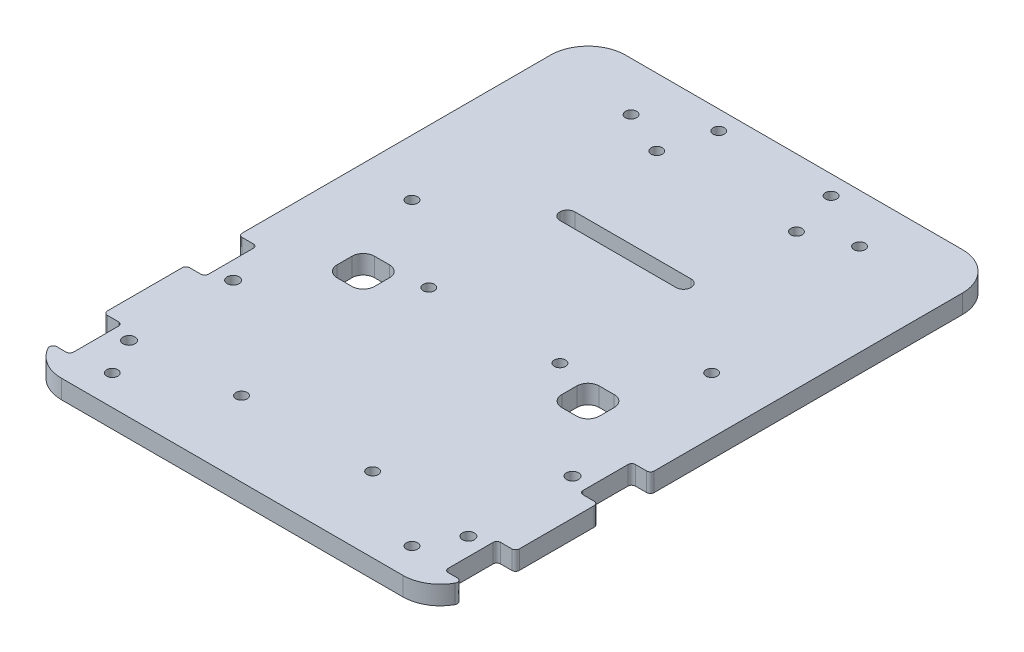
SolidWorks part; units mm, degrees
ref_plane "Front Plane" through (0, 0, 0) normal (0, 0, 1) x (1, 0, 0)
ref_plane "Top Plane" through (0, 0, 0) normal (0, 1, 0) x (1, 0, 0)
ref_plane "Right Plane" through (0, 0, 0) normal (1, 0, 0) x (0, 0, -1)
sketch "Sketch1" plane through (0, 0, 0) normal (0, 1, 0) x (1, 0, 0)
  line L0 (0, -75) -> (0, -43.3378) construction
  line L1 (-55, 75) -> (55, 75)
  line L2 (-55, 75) -> (-55, -75)
  line L3 (-55, -75) -> (55, -75)
  line L4 (55, 75) -> (55, -75)
  line L5 (-55, 75) -> (55, -75) construction
  line L6 (-55, -75) -> (55, 75) construction
  line L7 (-55, -43.3378) -> (55, -43.3378)
  line L8 (-55, -43.3378) -> (-45.3, -43.3378) construction
  line L9 (55, -43.3378) -> (45.3, -43.3378) construction
  line L10 (-45.3, -29.4378) -> (-45.3, -57.2378)
  line L11 (45.3, -29.4378) -> (45.3, -57.2378)
  line L12 (0, 75) -> (0, 62) construction
  line L13 (-30.5, 62) -> (30.5, 62)
  line L14 (0, 75) -> (0, 57) construction
  line L15 (-18.65, 57) -> (18.65, 57)
  line L16 (0, 75) -> (0, 30) construction
  line L17 (-55, 13) -> (55, 13) construction
  line L18 (-17.5, 32) -> (17.5, 32)
  line L19 (-17.5, 32) -> (-17.5, 28)
  line L20 (-17.5, 28) -> (17.5, 28)
  line L21 (17.5, 32) -> (17.5, 28)
  line L22 (-17.5, 32) -> (17.5, 28) construction
  line L23 (-17.5, 28) -> (17.5, 32) construction
  line L24 (-40, 13) -> (-40, -67) construction
  line L25 (40, 13) -> (40, -67) construction
  line L26 (-15, 69.8972) -> (15, 69.8972)
  line L27 (-35, -5) -> (-25, -5)
  line L28 (-35, -5) -> (-35, -15)
  line L29 (-35, -15) -> (-25, -15)
  line L30 (-25, -5) -> (-25, -15)
  line L31 (-35, -5) -> (-25, -15) construction
  line L32 (-35, -15) -> (-25, -5) construction
  line L33 (25, -5) -> (35, -5)
  line L34 (25, -5) -> (25, -15)
  line L35 (25, -15) -> (35, -15)
  line L36 (35, -5) -> (35, -15)
  line L37 (25, -5) -> (35, -15) construction
  line L38 (25, -15) -> (35, -5) construction
  line L39 (0, -75) -> (0, 28) construction
  line L40 (-17.5, -5) -> (17.5, -5)
  line L41 (-17.5, -55) -> (17.5, -55)
  line L42 (55, -43.3378) -> (55, -58.3378) construction
  line L43 (55, -43.3378) -> (55, -28.3378) construction
  line L50 (50, -18.3378) -> (55, -18.3378)
  line L51 (50, -18.3378) -> (50, -32.3378)
  line L52 (50, -32.3378) -> (55, -32.3378)
  line L53 (55, -18.3378) -> (55, -32.3378)
  line L54 (50, -54.3378) -> (55, -54.3378)
  line L55 (55, -68.3378) -> (55, -54.3378)
  line L56 (50, -68.3378) -> (55, -68.3378)
  line L57 (50, -68.3378) -> (50, -54.3378)
  line L58 (-50, -68.3378) -> (-50, -54.3378)
  line L59 (-50, -68.3378) -> (-55, -68.3378)
  line L60 (-55, -68.3378) -> (-55, -54.3378)
  line L61 (-50, -54.3378) -> (-55, -54.3378)
  line L62 (-50, -32.3378) -> (-55, -32.3378)
  line L63 (-55, -18.3378) -> (-55, -32.3378)
  line L64 (-50, -18.3378) -> (-55, -18.3378)
  line L65 (-50, -18.3378) -> (-50, -32.3378)
  circle A0 centre (-45.3, -29.4378) radius 1.6
  circle A1 centre (-45.3, -57.2378) radius 1.6
  circle A2 centre (45.3, -57.2378) radius 1.6
  circle A3 centre (45.3, -29.4378) radius 1.6
  circle A4 centre (30.5, 62) radius 1.5
  circle A5 centre (-30.5, 62) radius 1.5
  circle A6 centre (18.65, 57) radius 1.5
  circle A7 centre (-18.65, 57) radius 1.5
  circle A8 centre (-40, 13) radius 1.5
  circle A9 centre (40, 13) radius 1.5
  circle A10 centre (-40, -67) radius 1.5
  circle A11 centre (40, -67) radius 1.5
  circle A12 centre (-15, 69.8972) radius 1.5
  circle A13 centre (15, 69.8972) radius 1.5
  circle A14 centre (-17.5, -5) radius 1.5
  circle A15 centre (17.5, -5) radius 1.5
  circle A16 centre (-17.5, -55) radius 1.5
  circle A17 centre (17.5, -55) radius 1.5
  point P0 (0, 0)
  point P11 (0, -43.3378)
  point P16 (-45.3, -43.3378)
  point P19 (45.3, -43.3378)
  point P28 (0, 62)
  point P34 (0, 57)
  point P51 (-30, -10)
  point P56 (-30, -15)
  point P57 (30, -10)
  point P65 (0, 69.8972)
  point P71 (0, -5)
  point P74 (0, -55)
  dimension "D7" = 3.2
  dimension "D8" = 3.2
  dimension "D9" = 3.2
  dimension "D10" = 3.2
  dimension "D13" = 3
  dimension "D14" = 3
  dimension "D17" = 3
  dimension "D18" = 3
  dimension "D23" = 3
  dimension "D24" = 3
  dimension "D25" = 15
  dimension "D26" = 15
  dimension "D27" = 80
  dimension "D30" = 3
  dimension "D31" = 3
  dimension "D41" = 3
  dimension "D42" = 3
  dimension "D47" = 3
  dimension "D48" = 3
  dimension "D49" = 3
  dimension "D50" = 3
  dimension "D1" = 110
  dimension "D2" = 150
  dimension "D3" = 9.7
  dimension "D4" = 9.7
  dimension "D5" = 27.8
  dimension "D6" = 27.8
  dimension "D11" = 13
  dimension "D12" = 61
  dimension "D15" = 18
  dimension "D16" = 37.3
  dimension "D19" = 45
  dimension "D20" = 4
  dimension "D21" = 35
  dimension "D22" = 62
  dimension "D28" = 80
  dimension "D29" = 80
  dimension "D32" = 20
  dimension "D33" = 60
  dimension "D34" = 10
  dimension "D35" = 10
  dimension "D36" = 20
  dimension "D37" = 60
  dimension "D38" = 10
  dimension "D39" = 10
  dimension "D40" = 30
  dimension "D43" = 35
  dimension "D44" = 35
  dimension "D45" = 20
  dimension "D46" = 70
  dimension "D51" = 15
  dimension "D52" = 15
  dimension "D53" = 0
  dimension "D54" = 4
  dimension "D55" = 14
  dimension "D56" = 5
extrude "Boss-Extrude1" add sketch "Sketch1" along normal blind 5 contours A2 L7 A1 L2 L3 L4 A11 A10 | A3 L7 L4 L1 L2 A0 A9 A8 A7 A6 A5 A4 L18 L21 L20 L19 L27 L30 L29 L28 L33 L36 L35 L34 region at (0, 0, -16.4744) region at (0, 0, 59.0706)
fillet "Fillet1" radius 10 4 edges at (55, 2.5, -75) (55, 2.5, 75) (-55, 2.5, 75) (-55, 2.5, -75)
fillet "Fillet2" radius 2 4 edges at (-17.5, 2.5, -28) (-17.5, 2.5, -32) (17.5, 2.5, -28) (17.5, 2.5, -32)
fillet "Fillet3" radius 3 8 edges at (-35, 2.5, 15) (-35, 2.5, 5) (-25, 2.5, 15) (-25, 2.5, 5) (25, 2.5, 15) (35, 2.5, 15) (35, 2.5, 5) (25, 2.5, 5)
fillet "Fillet4" radius 1 8 edges at (-55, 2.5, 68.3378) (-55, 2.5, 18.3378) (-50, 2.5, 18.3378) (-50, 2.5, 68.3378) (-50, 2.5, 54.3378) (-50, 2.5, 32.3378) (-55, 2.5, 54.3378) (-55, 2.5, 32.3378)
fillet "Fillet5" radius 1 8 edges at (55, 2.5, 68.3378) (50, 2.5, 68.3378) (50, 2.5, 54.3378) (55, 2.5, 54.3378) (55, 2.5, 32.3378) (50, 2.5, 32.3378) (50, 2.5, 18.3378) (55, 2.5, 18.3378)
